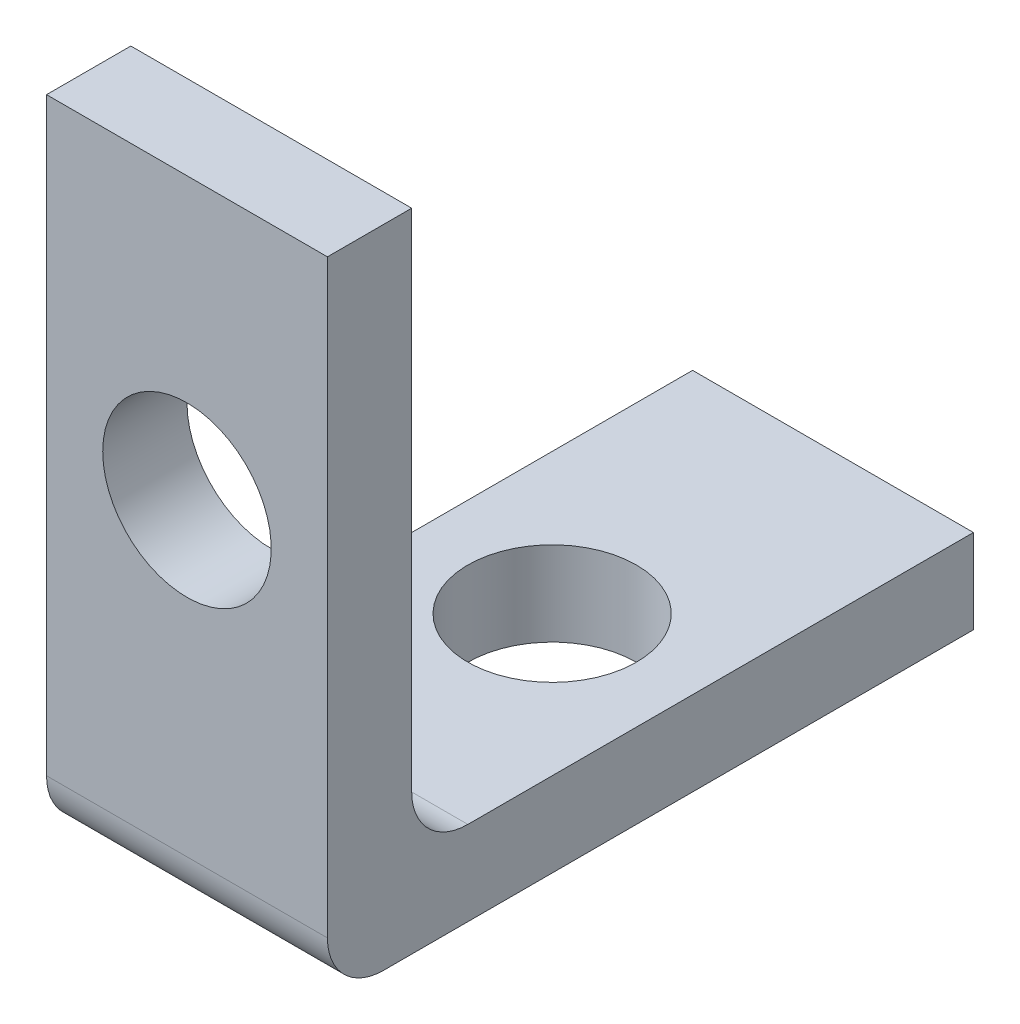
SolidWorks part; units mm, degrees
ref_plane "Front Plane" through (0, 0, 0) normal (0, 0, 1) x (1, 0, 0)
ref_plane "Top Plane" through (0, 0, 0) normal (0, 1, 0) x (1, 0, 0)
ref_plane "Right Plane" through (0, 0, 0) normal (1, 0, 0) x (0, 0, -1)
sketch "Sketch1" plane through (0, 0, 0) normal (0, 1, 0) x (1, 0, 0)
  line L1 (0, 0) -> (5, 0)
  line L2 (0, 0) -> (0, 10)
  line L3 (0, 10) -> (5, 10)
  line L4 (5, 0) -> (5, 10)
  dimension "D1" = 10
  dimension "D2" = 5
extrude "Boss-Extrude1" add sketch "Sketch1" along normal blind 1.5
sketch "Sketch2" plane through (0, 0, 0) normal (0, 0, 1) x (1, 0, 0)
  line L1 (0, 0) -> (5, 0)
  line L2 (0, 0) -> (0, 11.5)
  line L3 (0, 11.5) -> (5, 11.5)
  line L4 (5, 0) -> (5, 11.5)
  dimension "D1" = 10
  dimension "D2" = 5
extrude "Boss-Extrude2" add sketch "Sketch2" along normal blind 1.5
sketch "Sketch3" plane through (0, 1.5, 0) normal (0, 1, 0) x (1, 0, 0)
  line L0 (5, 10) -> (0, 10) construction
  line L2 (5, 0) -> (5, 10) construction
  circle A0 centre (2.5, 5) radius 1.5
  dimension "D1" = 5
  dimension "D2" = 2.5
extrude "Cut-Extrude1" cut sketch "Sketch3" against normal blind 10 and the other way blind 1.5 contours A0
sketch "Sketch4" plane through (0, 0, 0) normal (0, 0, -1) x (-1, 0, 0)
  line L0 (-5, 11.5) -> (0, 11.5) construction
  line L3 (0, 11.5) -> (0, 1.5) construction
  circle A0 centre (-2.5, 6.5) radius 1.5
  dimension "D2" = 3
  dimension "D1" = 5
  dimension "D3" = 2.5
extrude "Cut-Extrude2" cut sketch "Sketch4" against normal blind 10 and the other way blind 10 contours A0
fillet "Fillet1" radius 1 1 edges
fillet "Fillet2" radius 1 1 edges at (2.5, 0, 1.5)
